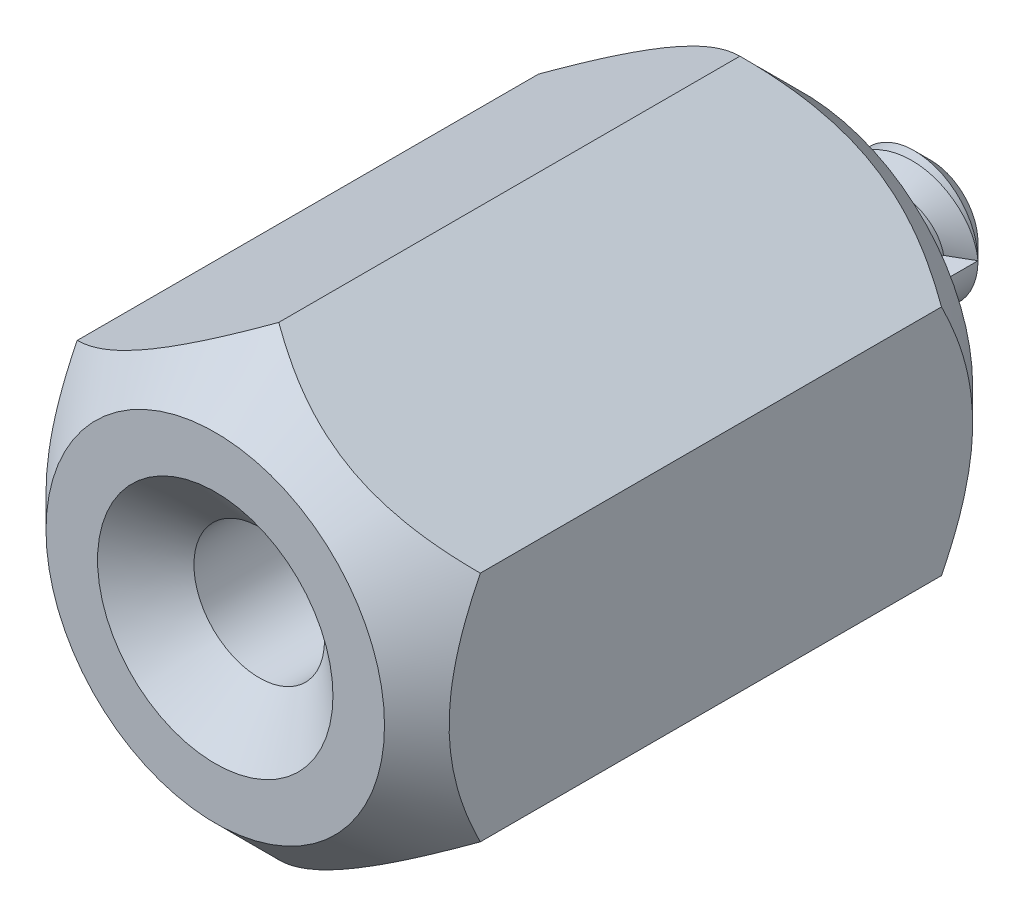
SolidWorks part; units mm, degrees
ref_plane "Front Plane" through (0, 0, 0) normal (0, 0, 1) x (1, 0, 0)
ref_plane "Top Plane" through (0, 0, 0) normal (0, 1, 0) x (1, 0, 0)
ref_plane "Right Plane" through (0, 0, 0) normal (1, 0, 0) x (0, 0, -1)
sketch "Sketch1" plane through (0, 0, 0) normal (0, 0, 1) x (1, 0, 0)
  line L1 (3.175, -1.8331) -> (3.175, 1.8331)
  line L2 (3.175, 1.8331) -> (0, 3.6662)
  line L3 (0, 3.6662) -> (-3.175, 1.8331)
  line L4 (-3.175, 1.8331) -> (-3.175, -1.8331)
  line L5 (-3.175, -1.8331) -> (0, -3.6662)
  line L6 (0, -3.6662) -> (3.175, -1.8331)
  circle A0 centre (0, 0) radius 3.175 construction
  dimension "D1" = 6.35
extrude "Boss-Extrude1" add sketch "Sketch1" along normal blind 4.6325 and the other way blind 4.6325
ref_axis "Axis1" through (0, 0, -0.635) along (0, 0, 1)
sketch "Sketch3" plane through (0, 0, 0) normal (1, 0, 0) x (0, 0, -1)
  line L0 (-4.6325, 3.6662) -> (4.6325, 3.6662) construction
  line L1 (-3.6325, 3.6662) -> (-4.6325, 2.6662)
  line L2 (-4.6325, 1.8331) -> (-4.6325, 3.6662) construction
  line L3 (-4.6325, 2.6662) -> (-4.6325, 3.6662)
  line L4 (-4.6325, 3.6662) -> (-3.6325, 3.6662)
  dimension "D1" = 1
  dimension "D2" = 45
revolve "Cut-Revolve2" cut sketch "Sketch3" angle 360 about axis through (0, 0, -0.635) along (0, 0, 1)
mirror "Mirror1" about plane through (0, 0, 0) normal (0, 0, 1) of "Cut-Revolve2"
hole_wizard "CSK for #1 Flat Head Machine Screw (100)1" positions "Sketch5" profile "Sketch4" countersink size "#1" standard "ANSI Inch"
sketch "Sketch5" plane through (0, 0, 4.6325) normal (0, 0, 1) x (1, 0, 0)
  point P0 (0, 0)
sketch "Sketch4" plane through (0, 0, 4.6325) normal (1, 0, 0) x (0, -1, 0)
  line L0 (0, 0) -> (0, 10.6181)
  line L1 (0, 10.6181) -> (1.0287, 10)
  line L2 (1.0287, 10) -> (1.0287, 0.6927)
  line L3 (1.0287, 0.6927) -> (1.8542, 0)
  line L5 (1.8542, 0) -> (0, 0)
  line L6 (-1.0287, 0.6927) -> (-1.8542, 0) construction
  line L10 (0, 10.6181) -> (-1.0287, 10) construction
  line L11 (0, -6.35) -> (0, 107.95) construction
  dimension "Hole Dia." = 2.0574
  dimension "Hole Depth" = 10
  dimension "Near C'Sink Dia." = 3.7084
  dimension "Near C'Sink Angle" = 100
  dimension "Drill Angle" = 118
sketch "Sketch6" plane through (0, 0, -4.6325) normal (0, 0, -1) x (-1, 0, 0)
  circle A0 centre (0, 0) radius 1
  dimension "D1" = 2
extrude "Boss-Extrude2" add sketch "Sketch6" along normal blind 2
chamfer "Chamfer1" distance 0.25 angle 45 1 edges at (-1, 0, -6.6325)
thread "Thread1" pitch 0.635 method cut profile "Thread Profile1" start angle 0, offset 0, length 2, pitch 0.635, diameter 2
ref_plane "Plane1" through (1, 0, -6.3825) normal (0, -1, 0) x (1, 0, 0)
sketch "Thread Profile1" plane through (1, 0, -6.3825) normal (0, -1, 0) x (1, 0, 0)
  line L0 (0, 0) -> (0, 0.635) construction
  line L11 (0, 0) -> (0, 0.5556)
  line L12 (0, 0.5556) -> (-0.3437, 0.3572)
  line L13 (-0.3437, 0.3572) -> (-0.3437, 0.1984)
  line L15 (-0.3437, 0.1984) -> (0, 0)
  line L17 (-0.3437, 0.2778) -> (0, 0.2778) construction
  point P2 (0, 0)
  dimension "Pitch" = 0.635
  dimension "Profile_Angle" = 60
  dimension "Profile_Land" = 0.1588
  dimension "Profile_Height" = 0.3437
